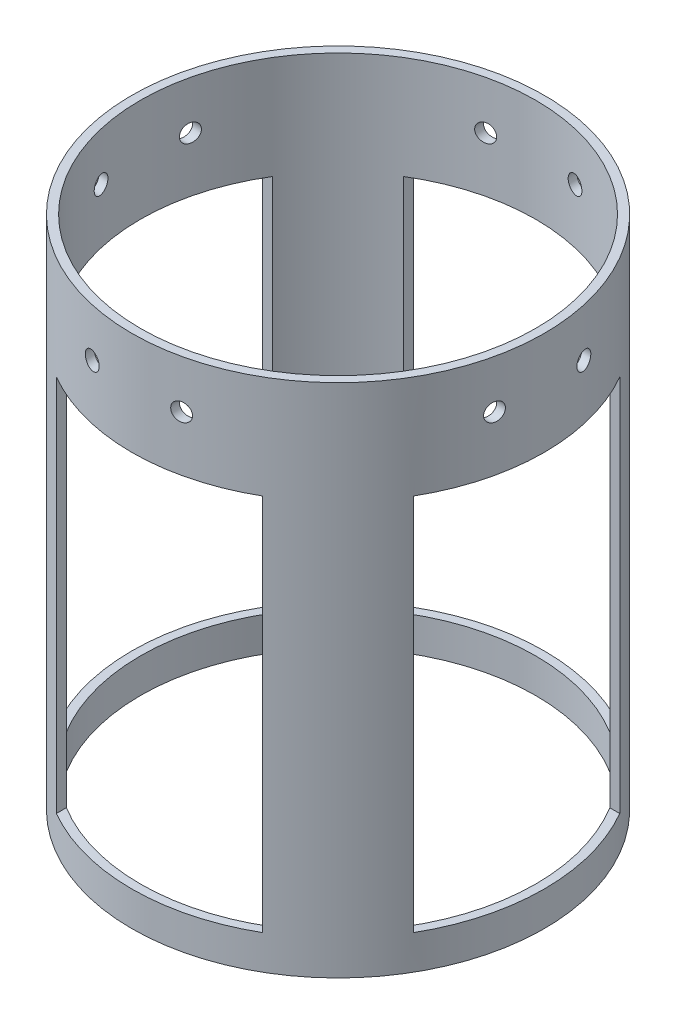
SolidWorks part; units mm, degrees
ref_plane "Front Plane" through (0, 0, 0) normal (0, 0, 1) x (1, 0, 0)
ref_plane "Top Plane" through (0, 0, 0) normal (0, 1, 0) x (1, 0, 0)
ref_plane "Right Plane" through (0, 0, 0) normal (1, 0, 0) x (0, 0, -1)
sketch "Sketch1" plane through (0, 0, 0) normal (0, 1, 0) x (1, 0, 0)
  circle A0 centre (0, 0) radius 76.2
  circle A1 centre (0, 0) radius 73.025
extrude "Boss-Extrude1" add sketch "Sketch1" along normal blind 190.5
sketch "Sketch5" plane through (0, 0, 0) normal (0, -1, 0) x (1, 0, 0)
  line L0 (0, 76.2) -> (0, -76.2) construction
  circle A0 centre (0, 0) radius 76.2 construction
ref_plane "Plane2" through (0, 0, -76.2) normal (0, 0, -1) x (-1, 0, 0)
sketch "Sketch6" plane through (0, 0, -76.2) normal (0, 0, -1) x (-1, 0, 0)
  line L0 (0, 190.5) -> (0, 152.4) construction
  line L1 (73.025, 190.5) -> (-73.025, 190.5) construction
  line L2 (0, 152.4) -> (-38.1, 152.4) construction
  line L7 (0, 152.4) -> (38.1, 152.4) construction
  line L8 (-38.1, 152.4) -> (38.1, 152.4)
  line L9 (-38.1, 152.4) -> (-38.1, 12.7)
  line L10 (38.1, 152.4) -> (38.1, 12.7)
  line L11 (-38.1, 12.7) -> (38.1, 12.7)
extrude "Cut-Extrude6" cut sketch "Sketch6" against normal blind 20.574
pattern_circular "CirPattern9" count 4 over 360 about axis through (0, 0, 0) along (0, 1, 0) of "Cut-Extrude6"
sketch "Sketch7" plane through (0, 0, -76.2) normal (0, 0, -1) x (-1, 0, 0)
  line L0 (0, 0) -> (0, 152.4) construction
  line L1 (0, 152.4) -> (0, 172.72) construction
  line L2 (16.51, 172.72) -> (-16.51, 172.72) construction
  circle A0 centre (-16.51, 172.72) radius 3.302
  circle A1 centre (16.51, 172.72) radius 3.302
  point P6 (0, 172.72)
extrude "Cut-Extrude7" cut sketch "Sketch7" against normal blind 17.78
pattern_circular "CirPattern10" count 4 over 360 about axis through (0, 190.5, 0) along (0, 1, 0) of "Cut-Extrude7"
